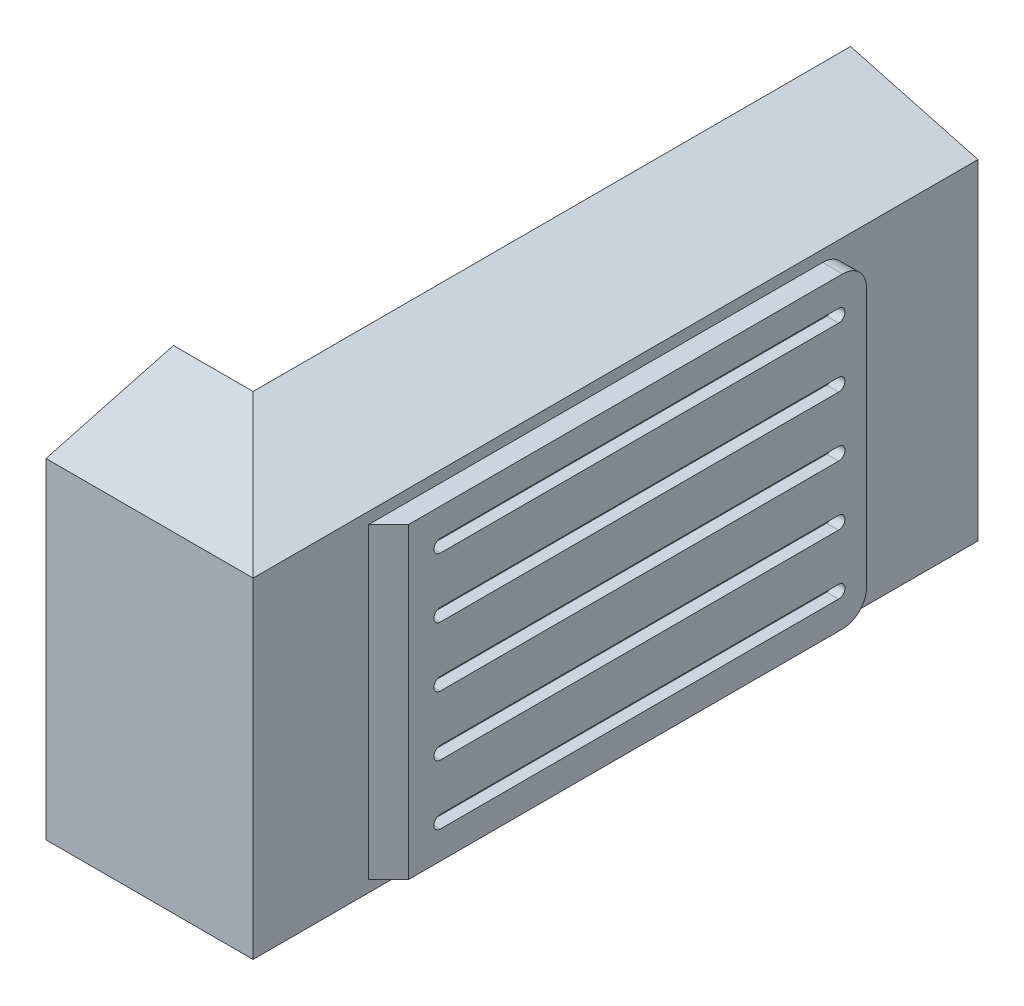
SolidWorks part; units mm, degrees
ref_plane "Front Plane" through (0, 0, 0) normal (0, 0, 1) x (1, 0, 0)
ref_plane "Top Plane" through (0, 0, 0) normal (0, 1, 0) x (1, 0, 0)
ref_plane "Right Plane" through (0, 0, 0) normal (1, 0, 0) x (0, 0, -1)
sketch "Sketch2" plane through (0, 0, 0) normal (0, 1, 0) x (1, 0, 0)
  line L0 (0, 0) -> (50, 0)
  line L1 (50, 0) -> (50, 180)
  dimension "D1" = 50
  dimension "D5" = 180
sketch "Sketch4" plane through (0, 0, 0) normal (1, 0, 0) x (0, 0, -1)
  line L0 (0, -40) -> (0, 40)
  line L1 (0, -40) -> (30, -48.0385)
  line L2 (30, -48.0385) -> (30, -50.0385)
  line L3 (30, -50.0385) -> (-2, -41.4641)
  line L4 (-2, -41.4641) -> (-2, 41.4641)
  line L5 (-2, 41.4641) -> (30, 50.0385)
  line L6 (30, 50.0385) -> (30, 48.0385)
  line L7 (30, 48.0385) -> (0, 40)
  line L8 (0, 0) -> (-2, 0) construction
  point P2 (0, 0)
  dimension "D1" = 2
  dimension "D2" = 80
  dimension "D3" = 30
  dimension "D4" = 105
sweep "Sweep1" add profiles "Sketch4" path "Sketch2"
sketch "Sketch6" plane through (50, 0, 0) normal (-1, 0, 0) x (0, 0, 1)
  line L0 (-40, 30) -> (-140, 30) construction
  line L1 (-40, 28.4) -> (-140, 28.4)
  line L2 (-40, 31.6) -> (-140, 31.6)
  line L3 (-40, 0) -> (-140, 0) construction
  line L4 (0, 0) -> (-180, 0) construction
  line L5 (-40, -1.6) -> (-140, -1.6)
  line L6 (-40, 1.6) -> (-140, 1.6)
  line L7 (-40, -30) -> (-140, -30) construction
  line L8 (-40, -31.6) -> (-140, -31.6)
  line L9 (-40, -28.4) -> (-140, -28.4)
  line L10 (-40, -15) -> (-140, -15) construction
  line L11 (-40, -16.6) -> (-140, -16.6)
  line L12 (-40, -13.4) -> (-140, -13.4)
  line L13 (-40, 15) -> (-140, 15) construction
  line L14 (-40, 13.4) -> (-140, 13.4)
  line L15 (-40, 16.6) -> (-140, 16.6)
  line L16 (-90, 30) -> (-90, 15) construction
  line L17 (-90, 15) -> (-90, 0) construction
  line L18 (-90, 0) -> (-90, -15) construction
  line L19 (-90, -15) -> (-90, -30) construction
  line L20 (0, 40) -> (0, -40) construction
  arc A0 (-40, 28.4) -> (-40, 31.6) centre (-40, 30) ccw
  arc A1 (-140, 31.6) -> (-140, 28.4) centre (-140, 30) ccw
  arc A2 (-40, -1.6) -> (-40, 1.6) centre (-40, 0) ccw
  arc A3 (-140, 1.6) -> (-140, -1.6) centre (-140, 0) ccw
  arc A4 (-40, -31.6) -> (-40, -28.4) centre (-40, -30) ccw
  arc A5 (-140, -28.4) -> (-140, -31.6) centre (-140, -30) ccw
  arc A6 (-40, -16.6) -> (-40, -13.4) centre (-40, -15) ccw
  arc A7 (-140, -13.4) -> (-140, -16.6) centre (-140, -15) ccw
  arc A8 (-40, 13.4) -> (-40, 16.6) centre (-40, 15) ccw
  arc A9 (-140, 16.6) -> (-140, 13.4) centre (-140, 15) ccw
  point P2 (-90, 30)
  point P7 (-90, 0)
  point P16 (-90, -30)
  point P23 (-90, -15)
  point P30 (-90, 15)
  dimension "D1" = 3.2
  dimension "D2" = 15
  dimension "D3" = 100
  dimension "D4" = 40
extrude "Cut-Extrude1" cut sketch "Sketch6" against normal through all
sketch "Sketch7" plane through (52, 0, 0) normal (1, 0, 0) x (0, 0, -1)
  line L0 (140, -31.6) -> (40, -31.6) construction
  line L3 (40, -28.4) -> (140, -28.4) construction
  line L4 (140, -16.6) -> (40, -16.6) construction
  line L13 (40, -13.4) -> (140, -13.4) construction
  line L16 (40, 1.6) -> (140, 1.6) construction
  line L19 (140, -1.6) -> (40, -1.6) construction
  line L22 (40, 0) -> (33, 0) construction
  line L23 (33, 38.6) -> (147, 38.6)
  line L24 (33, 38.6) -> (33, -38.6)
  line L25 (33, -38.6) -> (147, -38.6)
  line L26 (147, 38.6) -> (147, -38.6)
  line L27 (140, 0) -> (147, 0) construction
  line L28 (140, 13.4) -> (40, 13.4) construction
  line L29 (40, 16.6) -> (140, 16.6) construction
  line L30 (140, 28.4) -> (40, 28.4) construction
  line L31 (40, 31.6) -> (140, 31.6) construction
  line L32 (140, -31.6) -> (40, -31.6)
  line L33 (40, -28.4) -> (140, -28.4)
  line L34 (140, -16.6) -> (40, -16.6)
  line L35 (40, -13.4) -> (140, -13.4)
  line L36 (40, 1.6) -> (140, 1.6)
  line L37 (140, -1.6) -> (40, -1.6)
  line L38 (140, 13.4) -> (40, 13.4)
  line L39 (40, 16.6) -> (140, 16.6)
  line L40 (140, 28.4) -> (40, 28.4)
  line L41 (40, 31.6) -> (140, 31.6)
  arc A0 (40, -28.4) -> (40, -31.6) centre (40, -30) ccw construction
  arc A1 (140, -31.6) -> (140, -28.4) centre (140, -30) ccw construction
  arc A2 (140, -16.6) -> (140, -13.4) centre (140, -15) ccw construction
  arc A3 (40, -13.4) -> (40, -16.6) centre (40, -15) ccw construction
  arc A4 (140, -1.6) -> (140, 1.6) centre (140, 0) ccw construction
  arc A5 (40, 1.6) -> (40, -1.6) centre (40, 0) ccw construction
  arc A6 (40, 16.6) -> (40, 13.4) centre (40, 15) ccw construction
  arc A7 (140, 13.4) -> (140, 16.6) centre (140, 15) ccw construction
  arc A8 (140, 28.4) -> (140, 31.6) centre (140, 30) ccw construction
  arc A9 (40, 31.6) -> (40, 28.4) centre (40, 30) ccw construction
  arc A10 (40, -28.4) -> (40, -31.6) centre (40, -30) ccw
  arc A11 (140, -31.6) -> (140, -28.4) centre (140, -30) ccw
  arc A12 (140, -16.6) -> (140, -13.4) centre (140, -15) ccw
  arc A13 (40, -13.4) -> (40, -16.6) centre (40, -15) ccw
  arc A14 (140, -1.6) -> (140, 1.6) centre (140, 0) ccw
  arc A15 (40, 1.6) -> (40, -1.6) centre (40, 0) ccw
  arc A16 (40, 16.6) -> (40, 13.4) centre (40, 15) ccw
  arc A17 (140, 13.4) -> (140, 16.6) centre (140, 15) ccw
  arc A18 (140, 28.4) -> (140, 31.6) centre (140, 30) ccw
  arc A19 (40, 31.6) -> (40, 28.4) centre (40, 30) ccw
  point P30 (0, 0)
  point P31 (0, 0)
  dimension "D1" = 7
  dimension "D2" = 8.6
extrude "Boss-Extrude1" add sketch "Sketch7" along normal blind 5
sketch "Sketch9" plane through (50, 0, 0) normal (-1, 0, 0) x (0, 0, 1)
  line L0 (-140, 30) -> (-40, 30) construction
  line L1 (-140, 33.6) -> (-40, 33.6)
  line L2 (-140, 26.4) -> (-40, 26.4)
  line L3 (-140, 15) -> (-40, 15) construction
  line L4 (-140, 18.6) -> (-40, 18.6)
  line L5 (-140, 11.4) -> (-40, 11.4)
  line L6 (-140, 0) -> (-40, 0) construction
  line L7 (-140, 3.6) -> (-40, 3.6)
  line L8 (-140, -3.6) -> (-40, -3.6)
  line L9 (-140, -15) -> (-40, -15) construction
  line L10 (-140, -11.4) -> (-40, -11.4)
  line L11 (-140, -18.6) -> (-40, -18.6)
  line L12 (-140, -30) -> (-40, -30) construction
  line L13 (-140, -26.4) -> (-40, -26.4)
  line L14 (-140, -33.6) -> (-40, -33.6)
  line L15 (-40, 31.6) -> (-140, 31.6) construction
  arc A0 (-140, 33.6) -> (-140, 26.4) centre (-140, 30) ccw
  arc A1 (-40, 26.4) -> (-40, 33.6) centre (-40, 30) ccw
  arc A2 (-140, 18.6) -> (-140, 11.4) centre (-140, 15) ccw
  arc A3 (-40, 11.4) -> (-40, 18.6) centre (-40, 15) ccw
  arc A4 (-140, 3.6) -> (-140, -3.6) centre (-140, 0) ccw
  arc A5 (-40, -3.6) -> (-40, 3.6) centre (-40, 0) ccw
  arc A6 (-140, -11.4) -> (-140, -18.6) centre (-140, -15) ccw
  arc A7 (-40, -18.6) -> (-40, -11.4) centre (-40, -15) ccw
  arc A8 (-140, -26.4) -> (-140, -33.6) centre (-140, -30) ccw
  arc A9 (-40, -33.6) -> (-40, -26.4) centre (-40, -30) ccw
  point P4 (-90, 30)
  point P9 (-90, 15)
  point P18 (-90, 0)
  point P27 (-90, -15)
  point P36 (-90, -30)
  dimension "D1" = 2
extrude "Cut-Extrude2" cut sketch "Sketch9" against normal blind 4
fillet "Fillet1" radius 6 2 edges at (54.5, 38.6, -147) (54.5, -38.6, -147)
chamfer "Chamfer1" distance 6 angle 45 1 edges at (52, 0, -33)
sketch "Sketch8" plane through (13.8494, 51.6865, 0) normal (0.2588, 0.9659, 0) x (0.9659, -0.2588, 0)
  line L0 (-0.5036, 166.4856) -> (-0.5036, 28.5316) construction
  line L1 (7.3593, 166.4856) -> (7.3593, 28.5316)
  line L2 (-8.3664, 166.4856) -> (-8.3664, 28.5316)
  line L3 (39.4964, -2) -> (39.4964, 180) construction
  arc A0 (7.3593, 166.4856) -> (-8.3664, 166.4856) centre (-0.5036, 166.4856) ccw
  arc A1 (-8.3664, 28.5316) -> (7.3593, 28.5316) centre (-0.5036, 28.5316) ccw
  point P2 (-0.5036, 97.5086)
  dimension "D1" = 40
